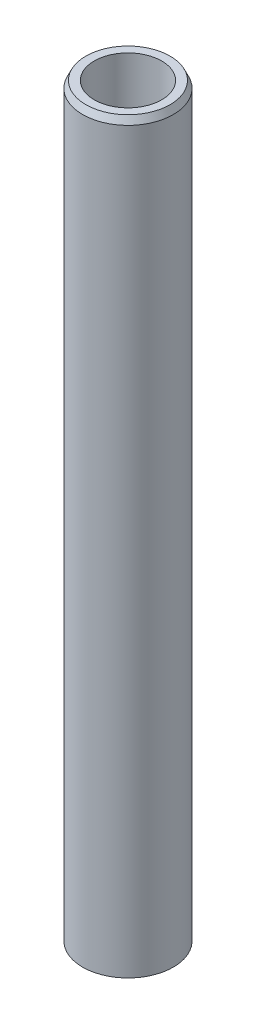
SolidWorks part; units mm, degrees
ref_plane "Front Plane" through (0, 0, 0) normal (0, 0, 1) x (1, 0, 0)
ref_plane "Top Plane" through (0, 0, 0) normal (0, 1, 0) x (1, 0, 0)
ref_plane "Right Plane" through (0, 0, 0) normal (1, 0, 0) x (0, 0, -1)
sketch "Sketch1" plane through (0, 0, 0) normal (0, 1, 0) x (1, 0, 0)
  circle A0 centre (0, 0) radius 12.5
  dimension "SHAFT_OD" = 25
extrude "Boss-Extrude1" add sketch "Sketch1" along normal blind 206.3305
sketch "Sketch2" plane through (0, 0, 0) normal (0, 1, 0) x (1, 0, 0)
  circle A0 centre (0, 0) radius 9.2904
  dimension "BORE_D" = 18.5807
extrude "Cut-Extrude1" cut sketch "Sketch2" along normal through all
chamfer "Chamfer1" distance 1.907 angle 25.093 2 edges at (0, 206.3305, 12.5) (0, 0, 12.5) first distance on face at (0, 206.3305, 12.5) first distance on face at (0, 0, 9.2904)
